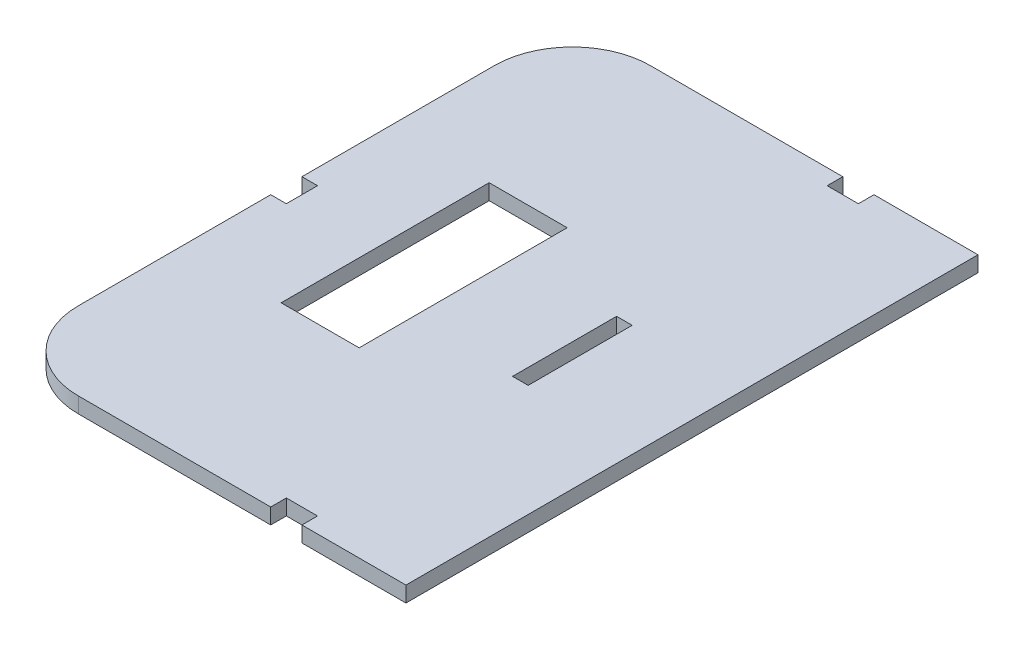
SolidWorks part; units mm, degrees
ref_plane "Спереди" through (0, 0, 0) normal (0, 0, 1) x (1, 0, 0)
ref_plane "Сверху" through (0, 0, 0) normal (0, 1, 0) x (1, 0, 0)
ref_plane "Справа" through (0, 0, 0) normal (1, 0, 0) x (0, 0, -1)
other "Configuration Table"
sketch "Эскиз4" plane through (0, 0, 0) normal (0, 1, 0) x (1, 0, 0)
  line L0 (78, 110) -> (78, 0)
  line L1 (0, 0) -> (52, 0)
  line L2 (0, 0) -> (0, 52)
  line L3 (0, 110) -> (52, 110)
  line L5 (58, 0) -> (78, 0)
  line L6 (55, 107) -> (55, 3) construction
  line L7 (52, 107) -> (55, 107)
  line L8 (55, 107) -> (58, 107)
  line L9 (52, 107) -> (52, 110)
  line L10 (58, 107) -> (58, 110)
  line L11 (58, 3) -> (58, 0)
  line L12 (55, 3) -> (58, 3)
  line L13 (55, 3) -> (52, 3)
  line L14 (52, 3) -> (52, 0)
  line L15 (3, 55) -> (3, 58)
  line L16 (3, 55) -> (3, 52)
  line L17 (3, 58) -> (0, 58)
  line L18 (3, 52) -> (0, 52)
  line L19 (0, 58) -> (0, 110)
  line L20 (58, 110) -> (78, 110)
  dimension "D1" = 110
  dimension "D2" = 55
  dimension "D3" = 3
  dimension "D4" = 3
  dimension "D5" = 3
  dimension "D6" = 3
  dimension "D7" = 3
  dimension "D8" = 3
  dimension "D9" = 3
  dimension "D10" = 20
extrude "Бобышка-Вытянуть3" add sketch "Эскиз4" along normal blind 3 contours L3 L10 L8 L9 L2 L17 L15 L16 L18 L1 L14 L13 L12 L11 | L7 L8 L10 L20 L0 L5 L11 L12 L13 L14 L1 L2 L18 L16 L15 L17 L19 L3 L9 region at (39.0116, 0, -55)
sketch "Sketch1" plane through (0, 3, 0) normal (0, 1, 0) x (1, 0, 0)
  line L0 (3, 52) -> (3, 58) construction
  line L13 (3, 55) -> (107, 55) construction
  line L15 (55, 107) -> (55, 3) construction
  line L16 (52, 107) -> (58, 107) construction
  line L17 (58, 3) -> (52, 3) construction
  line L19 (19, 75) -> (34, 75)
  line L20 (19, 75) -> (19, 35)
  line L21 (19, 35) -> (34, 35)
  line L22 (34, 75) -> (34, 35)
  line L23 (53.5, 65) -> (56.5, 65)
  line L24 (53.5, 65) -> (53.5, 45)
  line L25 (53.5, 45) -> (56.5, 45)
  line L26 (56.5, 65) -> (56.5, 45)
  dimension "D1" = 3
  dimension "D2" = 20
  dimension "D3" = 16
  dimension "D4" = 15
  dimension "D5" = 40
extrude "Cut-Extrude1" cut sketch "Sketch1" against normal blind 10
fillet "Fillet1" radius 15 2 edges at (0, 1.5, 0) (0, 1.5, -110)
